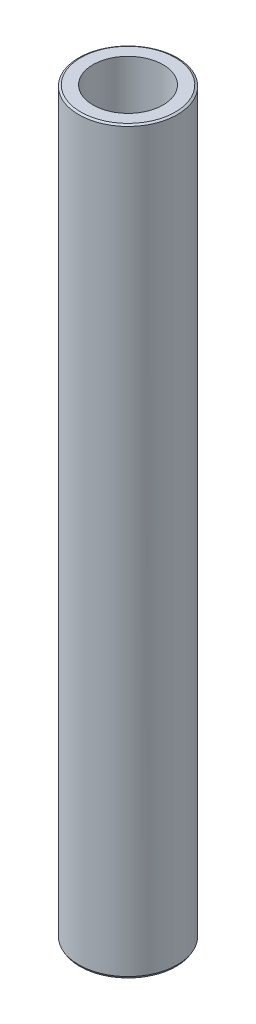
SolidWorks part; units mm, degrees
ref_plane "Front Plane" through (0, 0, 0) normal (0, 0, 1) x (1, 0, 0)
ref_plane "Top Plane" through (0, 0, 0) normal (0, 1, 0) x (1, 0, 0)
ref_plane "Right Plane" through (0, 0, 0) normal (1, 0, 0) x (0, 0, -1)
sketch "Sketch1" plane through (0, 0, 0) normal (0, 1, 0) x (1, 0, 0)
  circle A0 centre (0, 0) radius 40
  dimension "SHAFT_OD" = 80
extrude "Boss-Extrude1" add sketch "Sketch1" along normal blind 600
sketch "Sketch2" plane through (0, 0, 0) normal (0, 1, 0) x (1, 0, 0)
  circle A0 centre (0, 0) radius 28.4005
  dimension "BORE_D" = 56.8009
extrude "Cut-Extrude1" cut sketch "Sketch2" along normal through all
chamfer "Chamfer1" distance 0.9649 angle 60 2 edges at (0, 600, 40) (0, 0, 40) first distance on face at (0, 600, 40) first distance on face at (0, 0, 28.4005)
